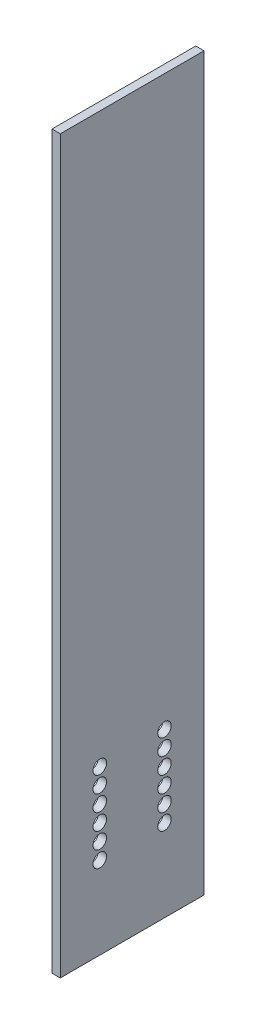
SolidWorks part; units mm, degrees
ref_plane "Front Plane" through (0, 0, 0) normal (0, 0, 1) x (1, 0, 0)
ref_plane "Top Plane" through (0, 0, 0) normal (0, 1, 0) x (1, 0, 0)
ref_plane "Right Plane" through (0, 0, 0) normal (1, 0, 0) x (0, 0, -1)
sketch "Sketch1" plane through (0, 0, 0) normal (1, 0, 0) x (0, 0, -1)
  line L1 (-28.2194, 143.51) -> (28.2194, 143.51)
  line L2 (-28.2194, 143.51) -> (-28.2194, -143.51)
  line L3 (-28.2194, -143.51) -> (28.2194, -143.51)
  line L4 (28.2194, 143.51) -> (28.2194, -143.51)
  line L5 (-28.2194, 143.51) -> (28.2194, -143.51) construction
  line L6 (-28.2194, -143.51) -> (28.2194, 143.51) construction
  point P0 (0, 0)
  dimension "D1" = 56.4388
  dimension "D2" = 287.02
extrude "Boss-Extrude1" add sketch "Sketch1" along normal blind 3.2512
sketch "Sketch2" plane through (0, 0, 0) normal (-1, 0, 0) x (0, 0, 1)
  line L0 (0, 143.51) -> (0, -143.51) construction
  line L1 (-28.2194, 143.51) -> (28.2194, 143.51) construction
  line L2 (28.2194, -143.51) -> (-28.2194, -143.51) construction
  point P7 (-12.7, -98.5012)
  point P9 (12.7, -98.5012)
  dimension "D1" = 12.7
  dimension "D2" = 45.0088
hole_wizard "#4 (0.209) Diameter Hole1" positions "Sketch3" profile "Sketch4" hole size "#4" standard "ANSI Inch" end condition through all
sketch "Sketch3" plane through (0, 0, 0) normal (-1, 0, 0) x (0, 0, 1)
  point P0 (-12.7, -98.5012)
  point P3 (12.7, -98.5012)
sketch "Sketch4" plane through (0, -98.5012, -12.7) normal (0, 1, 0) x (0, 0, 1)
  line L0 (0, 0) -> (0, 3.2512)
  line L1 (0, 3.2512) -> (2.6543, 3.2512)
  line L2 (2.6543, 3.2512) -> (2.6543, 0)
  line L5 (2.6543, 0) -> (0, 0)
  line L11 (0, -6.35) -> (0, 107.95) construction
  dimension "Thru Hole Dia." = 5.3086
  dimension "Thru Hole Depth" = 3.2512
pattern_linear "LPattern1" count 4 spacing 6.35 along (0, 1, 0) count 3 spacing 6.35 along (0, -1, 0) of "#4 (0.209) Diameter Hole1" pattern seed only yes
equation "\"motor offset\"=6mm"
equation "\"thickness0.25\"=0.225in"
equation "\"thickness0.125\"=0.122in"
equation "\"thickness_acrylic0.1\"= 0.1in"
equation "\"D1@Sketch1\"=\"thickness_acrylic0.1\"+\"thickness0.125\"+2"
equation "\"D2@Sketch2\"=\"thickness0.125\"+0.5+1.15"
